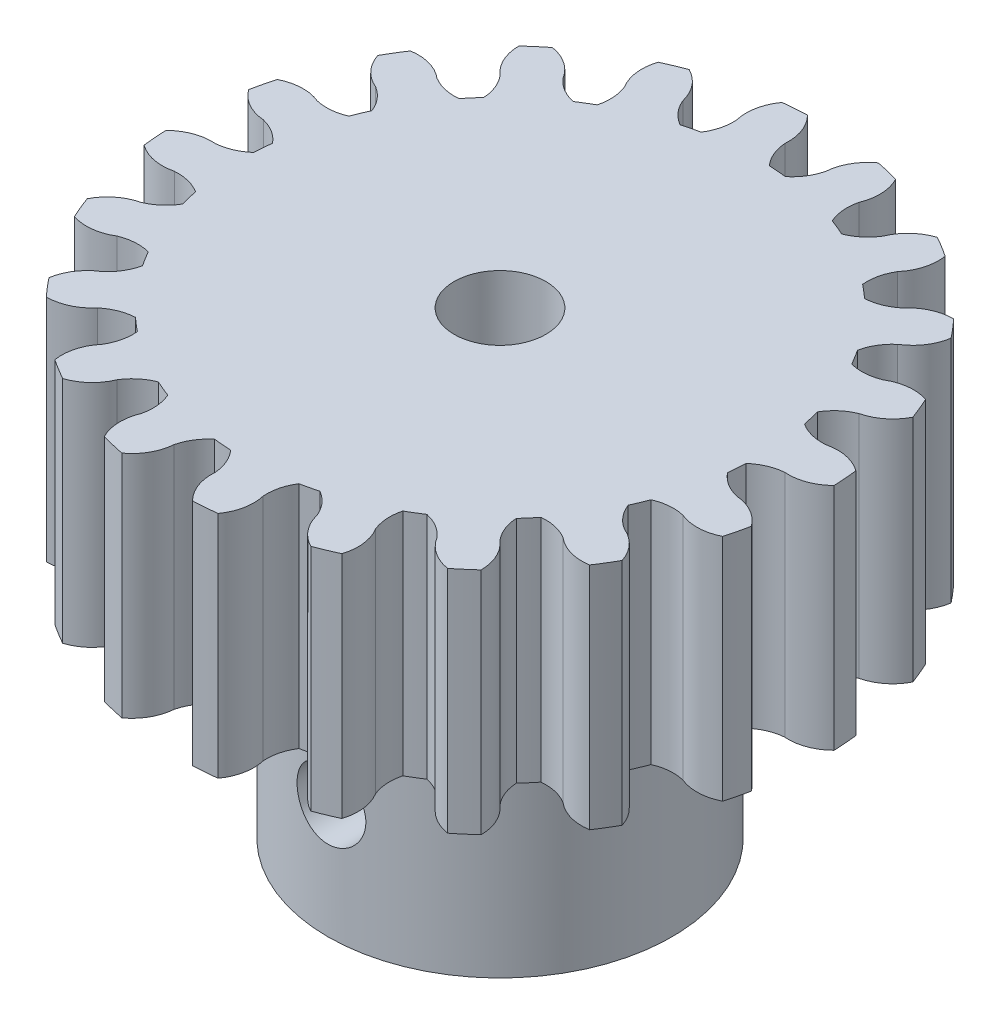
SolidWorks part; units mm, degrees
ref_plane "Front Plane" through (0, 0, 0) normal (0, 0, 1) x (1, 0, 0)
ref_plane "Top Plane" through (0, 0, 0) normal (0, 1, 0) x (1, 0, 0)
ref_plane "Right Plane" through (0, 0, 0) normal (1, 0, 0) x (0, 0, -1)
sketch "Sketch1" plane through (0, 0, 0) normal (0, 1, 0) x (1, 0, 0)
  circle A0 centre (0, 0) radius 14
  circle A1 centre (0, 0) radius 5
  circle A2 centre (0, 0) radius 6
  dimension "D1" = 28
extrude "Boss-Extrude1" add sketch "Sketch1" along normal blind 10 contours A0
sketch "Sketch3" plane through (0, 10, 0) normal (0, 1, 0) x (1, 0, 0)
  arc A0 (2.8804, 13.8027) -> (-0.683, 14.0834) centre (0, 0) ccw
  arc A2 (1.2626, 11.1789) -> (0.5039, 11.2387) centre (0, 0) ccw
  arc A3 (1.2626, 11.1789) -> (1.9446, 12.2626) centre (0, 12.73) ccw
  arc A5 (0, 12.4158) -> (-0.683, 14.0834) centre (-1.9938, 12.5729) ccw
  arc A6 (2.8804, 13.8027) -> (1.9446, 12.2626) centre (3.9384, 12.1054) ccw
  arc A8 (0, 12.4158) -> (0.5039, 11.2387) centre (1.9938, 12.5729) ccw
  dimension "D2" = 22.5
extrude "Cut-Extrude3" cut sketch "Sketch3" against normal blind 18
pattern_circular "CirPattern2" count 20 over 360 about axis through (0, 10, 0) along (0, 1, 0) of "Cut-Extrude3"
sketch "Sketch4" plane through (0, 0, 0) normal (0, -1, 0) x (-1, 0, 0)
  circle A0 centre (0, 0) radius 2
extrude "Cut-Extrude4" cut sketch "Sketch4" against normal blind 120
sketch "Sketch5" plane through (0, 0, 0) normal (0, -1, 0) x (1, 0, 0)
  circle A0 centre (0, 0) radius 2
  circle A1 centre (0, 0) radius 7.5
extrude "Boss-Extrude2" add sketch "Sketch5" along normal blind 10
sketch "Sketch6" plane through (0, 0, 0) normal (0, 0, 1) x (1, 0, 0)
  line L0 (0, -10) -> (0, -5) construction
  line L1 (-7.5, -10) -> (7.5, -10) construction
  circle A0 centre (0, -5) radius 1.5
extrude "Cut-Extrude5" cut sketch "Sketch6" along normal blind 21 and the other way blind 21
